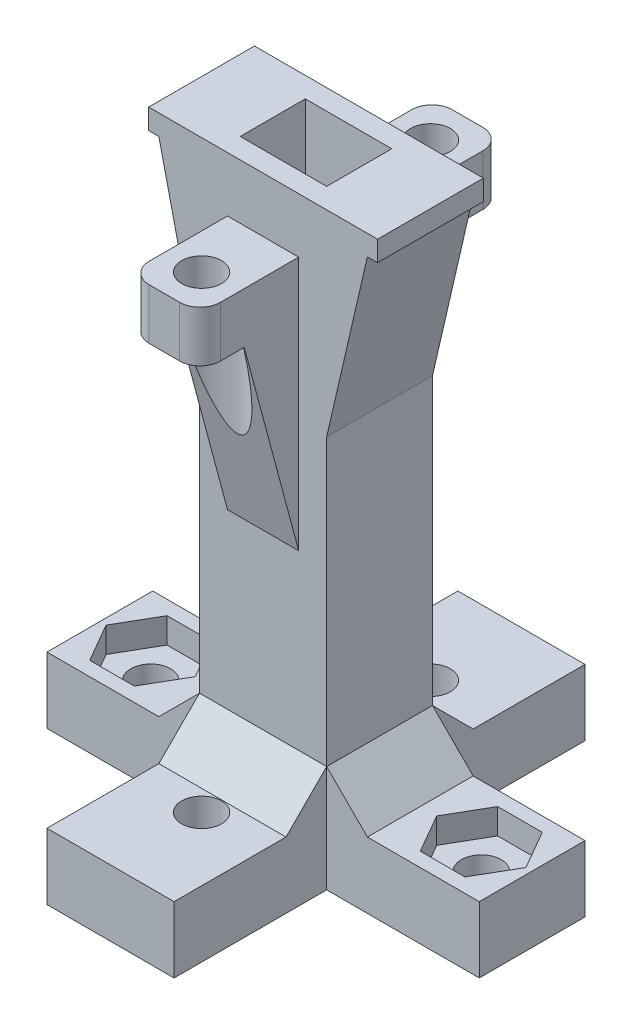
SolidWorks part; units mm, degrees
ref_plane "Front Plane" through (0, 0, 0) normal (0, 0, 1) x (1, 0, 0)
ref_plane "Top Plane" through (0, 0, 0) normal (0, 1, 0) x (1, 0, 0)
ref_plane "Right Plane" through (0, 0, 0) normal (1, 0, 0) x (0, 0, -1)
sketch "Sketch1" plane through (0, 0, 0) normal (0, 1, 0) x (1, 0, 0)
  line L1 (-7.9375, -5.2705) -> (7.9375, -5.2705)
  line L2 (-7.9375, -5.2705) -> (-7.9375, 7.9375)
  line L3 (-7.9375, 7.9375) -> (7.9375, 7.9375)
  line L4 (7.9375, -5.2705) -> (7.9375, 7.9375)
  dimension "D1" = 13.208
  dimension "D2" = 15.875
  dimension "D3" = 7.9375
  dimension "D4" = 7.9375
extrude "Boss-Extrude1" add sketch "Sketch1" along normal blind 73.533
shell "Shell1" thickness 2.54 removed face at (0, 73.533, -1.3335) removed face at (0, 0, -1.3335)
sketch "Sketch3" plane through (0, 0, -7.9375) normal (0, 0, -1) x (-1, 0, 0)
  line L1 (-4.445, 66.675) -> (4.445, 66.675)
  line L2 (-4.445, 66.675) -> (-4.445, 60.325)
  line L3 (-4.445, 60.325) -> (4.445, 60.325)
  line L4 (4.445, 66.675) -> (4.445, 60.325)
  line L5 (7.9375, 73.533) -> (7.9375, 0) construction
  line L6 (-7.9375, 73.533) -> (7.9375, 73.533) construction
  dimension "D1" = 6.35
  dimension "D2" = 8.89
  dimension "D3" = 3.4925
  dimension "D4" = 13.208
extrude "Boss-Extrude2" add sketch "Sketch3" along normal blind 12.319
sketch "Sketch4" plane through (0, 0, 5.2705) normal (0, 0, 1) x (1, 0, 0)
  line L1 (-4.445, 66.675) -> (4.445, 66.675)
  line L2 (-4.445, 66.675) -> (-4.445, 60.325)
  line L3 (-4.445, 60.325) -> (4.445, 60.325)
  line L4 (4.445, 66.675) -> (4.445, 60.325)
  line L5 (7.9375, 73.533) -> (7.9375, 0) construction
  line L6 (-7.9375, 73.533) -> (7.9375, 73.533) construction
  dimension "D1" = 6.35
  dimension "D2" = 8.89
  dimension "D3" = 3.4925
  dimension "D4" = 13.208
extrude "Boss-Extrude3" add sketch "Sketch4" along normal blind 12.319 contours L3 L4 L1 L2
sketch "Sketch5" plane through (-7.9375, 0, 0) normal (-1, 0, 0) x (0, 0, 1)
  line L0 (5.2705, 73.533) -> (5.2705, 0) construction
  line L1 (-7.9375, 0) -> (5.2705, 0)
  line L2 (-7.9375, 0) -> (-7.9375, 8.255)
  line L3 (-7.9375, 8.255) -> (5.2705, 8.255)
  line L4 (5.2705, 0) -> (5.2705, 8.255)
  dimension "D1" = 8.255
extrude "Boss-Extrude4" add sketch "Sketch5" along normal blind 19.05
sketch "Sketch6" plane through (0, 0, -7.9375) normal (0, 0, -1) x (-1, 0, 0)
  line L1 (7.9375, 8.255) -> (-7.9375, 8.255)
  line L2 (7.9375, 8.255) -> (7.9375, 0)
  line L3 (7.9375, 0) -> (-7.9375, 0)
  line L4 (-7.9375, 8.255) -> (-7.9375, 0)
extrude "Boss-Extrude5" add sketch "Sketch6" along normal blind 19.05
sketch "Sketch7" plane through (7.9375, 0, 0) normal (1, 0, 0) x (0, 0, -1)
  line L1 (7.9375, 8.255) -> (-5.2705, 8.255)
  line L2 (7.9375, 8.255) -> (7.9375, 0)
  line L3 (7.9375, 0) -> (-5.2705, 0)
  line L4 (-5.2705, 8.255) -> (-5.2705, 0)
extrude "Boss-Extrude6" add sketch "Sketch7" along normal blind 19.05
sketch "Sketch8" plane through (0, 0, 5.2705) normal (0, 0, 1) x (1, 0, 0)
  line L0 (-26.9875, 0) -> (26.9875, 0) construction
  line L1 (7.9375, 8.255) -> (-7.9375, 8.255)
  line L2 (7.9375, 8.255) -> (7.9375, 0)
  line L3 (7.9375, 0) -> (-7.9375, 0)
  line L4 (-7.9375, 8.255) -> (-7.9375, 0)
  dimension "D1" = 15.875
extrude "Boss-Extrude7" add sketch "Sketch8" along normal blind 19.05
sketch "Sketch9" plane through (0, 73.533, 0) normal (0, 1, 0) x (1, 0, 0)
  line L3 (0, 20.2565) -> (0, 15.621) construction
  line L7 (-4.445, 20.2565) -> (4.445, 20.2565) construction
  line L8 (0, -17.5895) -> (0, -12.954) construction
  line L10 (-4.445, -17.5895) -> (4.445, -17.5895) construction
  circle A0 centre (0, 15.621) radius 2.4892
  circle A1 centre (0, -12.954) radius 2.4892
  dimension "D1" = 4.9784
  dimension "D2" = 4.9784
  dimension "D3" = 28.575
extrude "Cut-Extrude1" cut sketch "Sketch9" against normal through all
sketch "Sketch11" plane through (0, 0, 0) normal (0, -1, 0) x (-1, 0, 0)
  line L2 (-26.9875, 1.3335) -> (26.9875, 1.3335) construction
  line L3 (-26.9875, -5.2705) -> (-26.9875, 7.9375) construction
  line L4 (26.9875, 7.9375) -> (26.9875, -5.2705) construction
  circle A1 centre (20.6375, 1.3335) radius 2.4892
  circle A3 centre (-20.6375, 1.3335) radius 2.4892
  point P16 (0, 1.3335)
  dimension "D6" = 4.9784
  dimension "D7" = 4.9784
  dimension "D5" = 6.35
  dimension "D4" = 6.35
extrude "Cut-Extrude2" cut sketch "Sketch11" against normal up to next
fillet "Fillet3" radius 2.54 4 edges at (4.445, 63.5, -20.2565) (-4.445, 63.5, -20.2565) (4.445, 63.5, 17.5895) (-4.445, 63.5, 17.5895)
chamfer "Chamfer2" distance 25.4 angle 15 2 edges at (0, 60.325, 5.2705) (0, 60.325, -7.9375) first distance on face at (0, 63.5, 5.2705) first distance on face at (0, 63.5, -7.9375)
sketch "Sketch12" plane through (0, 60.325, 0) normal (0, -1, 0) x (1, 0, 0)
  circle A0 centre (0, -15.621) radius 4.445
  circle A1 centre (0, 12.954) radius 4.445
  dimension "D1" = 8.89
extrude "Cut-Extrude3" cut sketch "Sketch12" along normal up to surface (52.07 mm away) up to face at (-20.6375, 8.255, -3.8227)
sketch "Sketch13" plane through (0, 73.533, 0) normal (0, 1, 0) x (1, 0, 0)
  line L0 (-5.3975, -2.7305) -> (5.3975, -2.7305) construction
  line L1 (14.2875, 7.9375) -> (-14.2875, 7.9375)
  line L2 (14.2875, 7.9375) -> (14.2875, -5.2705)
  line L3 (14.2875, -5.2705) -> (-14.2875, -5.2705)
  line L4 (-14.2875, 7.9375) -> (-14.2875, -5.2705)
  line L5 (5.3975, 5.3975) -> (-5.3975, 5.3975)
  line L6 (5.3975, 5.3975) -> (5.3975, -2.7305)
  line L7 (5.3975, -2.7305) -> (-5.3975, -2.7305)
  line L8 (-5.3975, 5.3975) -> (-5.3975, -2.7305)
  line L9 (7.9375, 7.9375) -> (-7.9375, 7.9375) construction
  line L10 (-7.9375, -5.2705) -> (7.9375, -5.2705) construction
  line L11 (7.9375, -5.2705) -> (7.9375, 7.9375) construction
  line L12 (-7.9375, 7.9375) -> (-7.9375, -5.2705) construction
  dimension "D1" = 6.35
  dimension "D2" = 6.35
extrude "Boss-Extrude8" add sketch "Sketch13" against normal blind 2.54
chamfer "Chamfer3" distance 5.08 angle 77 2 edges at (7.9375, 70.993, -1.3335) (-7.9375, 70.993, -1.3335) first distance on face at (11.1125, 70.993, -1.3335) first distance on face at (-11.1125, 70.993, -1.3335)
chamfer "Chamfer4" distance 5.08 angle 45 2 edges
chamfer "Chamfer5" distance 5.08 angle 45 2 edges
sketch "Sketch14" plane through (0, 8.255, 0) normal (0, 1, 0) x (1, 0, 0)
  line L1 (-26.2101, 1.3335) -> (-23.4238, -3.4925)
  line L2 (-23.4238, -3.4925) -> (-17.8512, -3.4925)
  line L3 (-17.8512, -3.4925) -> (-15.0649, 1.3335)
  line L4 (-15.0649, 1.3335) -> (-17.8512, 6.1595)
  line L5 (-17.8512, 6.1595) -> (-23.4238, 6.1595)
  line L6 (-23.4238, 6.1595) -> (-26.2101, 1.3335)
  circle A0 centre (-20.6375, 1.3335) radius 4.826 construction
  dimension "D1" = 9.652
extrude "Cut-Extrude4" cut sketch "Sketch14" against normal blind 3.175
sketch "Sketch15" plane through (0, 8.255, 0) normal (0, 1, 0) x (1, 0, 0)
  line L1 (15.0649, 1.3335) -> (17.8512, -3.4925)
  line L2 (17.8512, -3.4925) -> (23.4238, -3.4925)
  line L3 (23.4238, -3.4925) -> (26.2101, 1.3335)
  line L4 (26.2101, 1.3335) -> (23.4238, 6.1595)
  line L5 (23.4238, 6.1595) -> (17.8512, 6.1595)
  line L6 (17.8512, 6.1595) -> (15.0649, 1.3335)
  circle A0 centre (20.6375, 1.3335) radius 4.826 construction
  dimension "D1" = 9.652
extrude "Cut-Extrude5" cut sketch "Sketch15" against normal blind 3.175
